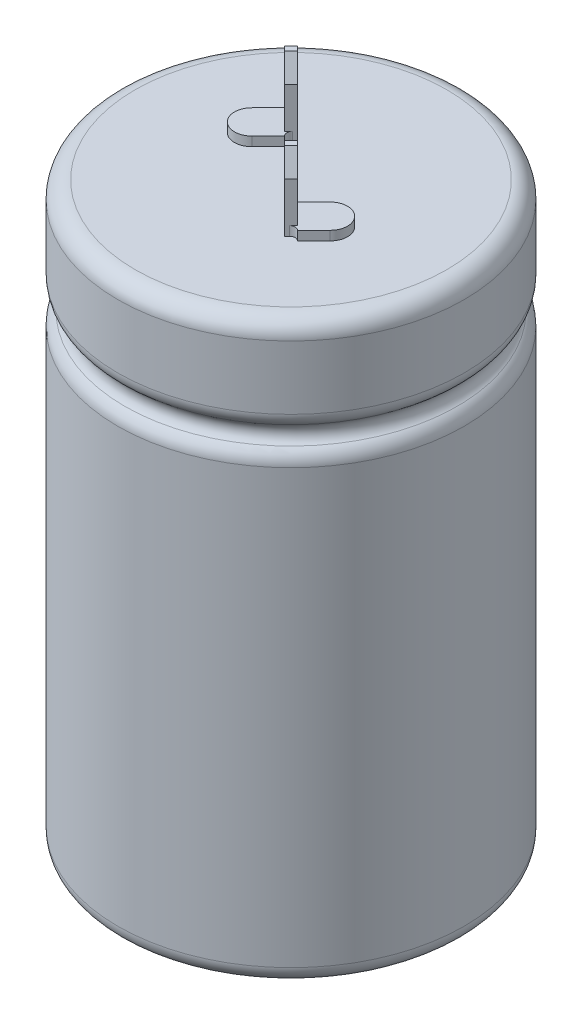
SolidWorks part; units mm, degrees
ref_plane "Front" through (0, 0, 0) normal (0, 0, 1) x (1, 0, 0)
ref_plane "Top" through (0, 0, 0) normal (0, 1, 0) x (1, 0, 0)
ref_plane "Right" through (0, 0, 0) normal (1, 0, 0) x (0, 0, -1)
sketch "Эскиз2" plane through (0, 0, 0) normal (0, 0, 1) x (1, 0, 0)
  line L0 (0, 0) -> (0, 86.546) construction
  line L1 (0, 0) -> (-15, 0)
  line L2 (-15, 0) -> (-15, 40)
  line L3 (-15, 42) -> (-15, 50)
  line L4 (-15, 50) -> (0, 50)
  line L5 (0, 0) -> (0, 50)
  arc A0 (-15, 40) -> (-15, 42) centre (-15, 41) ccw
  dimension "D3" = 1
  dimension "D1" = 15
  dimension "D2" = 40
  dimension "D4" = 8
  dimension "D5" = 50
revolve "Повернуть1" add sketch "Эскиз2" angle 360 about L0
fillet "Скругление1" radius 1.5 4 edges at (0, 42, -15) (0, 40, -15) (0, 0, -15) (0, 50, -15)
sketch "Эскиз3" plane through (0, 50, 0) normal (0, 1, 0) x (1, 0, 0)
  line L0 (0, 19.0334) -> (0, -20.0884) construction
  line L1 (-21.1088, 0) -> (22.0013, 0) construction
  line L2 (13.3862, -13.3862) -> (-13.3862, 13.3862) construction
  line L3 (-4.5255, 3.9598) -> (-3.1113, 2.5456)
  line L4 (-4.5255, 3.9598) -> (-3.9598, 4.5255)
  line L5 (-3.1113, 2.5456) -> (-2.5456, 3.1113)
  line L6 (-3.9598, 4.5255) -> (-2.5456, 3.1113)
  line L7 (-4.5255, 3.9598) -> (-2.5456, 3.1113) construction
  line L8 (-3.1113, 2.5456) -> (-3.9598, 4.5255) construction
  line L9 (3.9598, -4.5255) -> (2.5456, -3.1113)
  line L10 (3.9598, -4.5255) -> (4.5255, -3.9598)
  line L11 (2.5456, -3.1113) -> (3.1113, -2.5456)
  line L12 (4.5255, -3.9598) -> (3.1113, -2.5456)
  line L13 (3.9598, -4.5255) -> (3.1113, -2.5456) construction
  line L14 (2.5456, -3.1113) -> (4.5255, -3.9598) construction
  point P8 (-3.5355, 3.5355)
  point P9 (0, 0)
  point P10 (3.5355, -3.5355)
  dimension "D2" = 0.8
  dimension "D3" = 2
  dimension "D4" = 5
  dimension "D5" = 0.8
  dimension "D1" = 45
  dimension "D6" = 2
  dimension "D7" = 5
extrude "Бобышка-Вытянуть4" add sketch "Эскиз3" along normal blind 6.3
sketch "Эскиз5" plane through (0, 50, 0) normal (0, 1, 0) x (1, 0, 0)
  line L0 (-2.7577, 2.192) -> (-4.879, 4.3134)
  line L2 (-4.5255, 3.9598) -> (-3.1113, 2.5456) construction
  line L3 (-4.879, 4.3134) -> (-6.2933, 2.8991)
  line L4 (-2.7577, 2.192) -> (-4.1719, 0.7778)
  line L5 (4.879, -4.3134) -> (2.7577, -2.192)
  line L7 (4.5255, -3.9598) -> (3.1113, -2.5456) construction
  line L8 (2.7577, -2.192) -> (4.1719, -0.7778)
  line L9 (4.879, -4.3134) -> (6.2933, -2.8991)
  arc A0 (-6.2933, 2.8991) -> (-4.1719, 0.7778) centre (-5.2326, 1.8385) ccw
  arc A1 (4.1719, -0.7778) -> (6.2933, -2.8991) centre (5.2326, -1.8385) cw
  point P3 (-3.8184, 3.2527)
  point P11 (3.8184, -3.2527)
  dimension "D1" = 3
  dimension "D2" = 2
  dimension "D3" = 3
  dimension "D4" = 2
  dimension "D5" = 2
extrude "Бобышка-Вытянуть5" add sketch "Эскиз5" along normal blind 0.8
chamfer "Фаска2" distance 2 angle 20 4 edges at (4.2426, 56.3, 4.2426) (2.8284, 56.3, 2.8284) (-4.2426, 56.3, -4.2426) (-2.8284, 56.3, -2.8284) first distance on face at (4.2992, 52.68, 4.1861) first distance on face at (2.885, 52.68, 2.7719) first distance on face at (-4.2992, 52.68, -4.1861) first distance on face at (-2.885, 52.68, -2.7719)
fillet "Скругление4" radius 0.5 4 edges at (3.1113, 50.4, 2.5456) (4.5255, 50.4, 3.9598) (-4.5255, 50.4, -3.9598) (-3.1113, 50.4, -2.5456)
